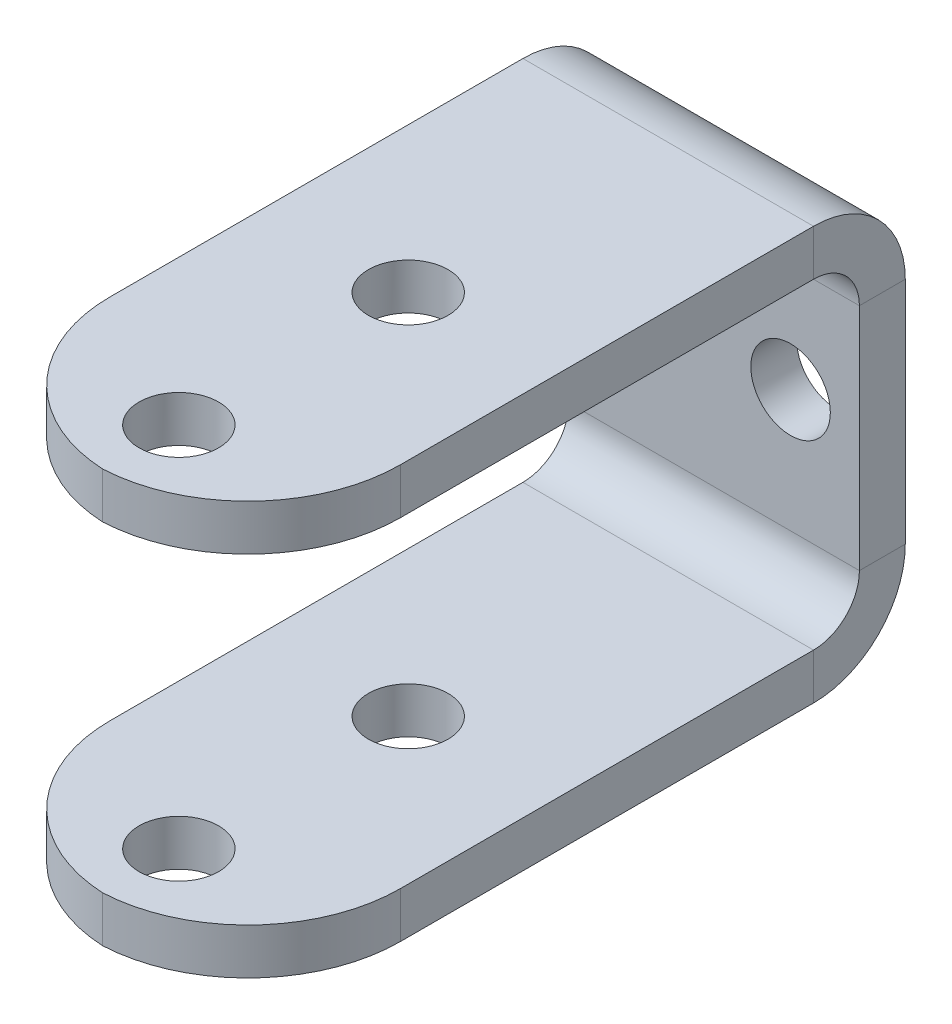
SolidWorks part; units mm, degrees
note: The reader was unsure of these and kept them because the rebuilt part matched: flange length of "Edge-Flange1".
ref_plane "Front Plane" through (0, 0, 0) normal (0, 0, 1) x (1, 0, 0)
ref_plane "Top Plane" through (0, 0, 0) normal (0, 1, 0) x (1, 0, 0)
ref_plane "Right Plane" through (0, 0, 0) normal (1, 0, 0) x (0, 0, -1)
sketch "Sketch1" plane through (0, 0, 0) normal (0, 0, 1) x (1, 0, 0)
  line L1 (-9.5, -13.5) -> (9.5, -13.5)
  line L2 (-9.5, -13.5) -> (-9.5, 13.5)
  line L3 (-9.5, 13.5) -> (9.5, 13.5)
  line L4 (9.5, -13.5) -> (9.5, 13.5)
  line L5 (-9.5, -13.5) -> (9.5, 13.5) construction
  line L6 (-9.5, 13.5) -> (9.5, -13.5) construction
  point P0 (0, 0)
  dimension "D1" = 19
  dimension "D2" = 27
base flange "Base-Flange1" sketch "Sketch1" thickness 3 reverse thickness direction no parameters "D1"=3
edge flange "Edge-Flange1" sketch "Sketch10" flange profiles "Sketch10", "Sketch11" flange angle 90 flange length 40 flange position material inside bend radius 3 thickness 3 relief rectangular parameters "D6"=10, "D8"=1
sketch "Sketch10" plane through (0, 13.5, 0) normal (0, 1, 0) x (-1, 0, 0)
  line L0 (-9.5, 0) -> (9.5, 0) construction
  line L1 (-9.5, 0) -> (9.5, 0)
  line L2 (-9.5, 0) -> (-9.5, 40)
  line L3 (-9.5, 40) -> (9.5, 40)
  line L4 (9.5, 40) -> (9.5, 0)
sketch "Sketch11" plane through (0, -13.5, 0) normal (0, -1, 0) x (1, 0, 0)
  line L0 (-9.5, 0) -> (9.5, 0) construction
  line L1 (-9.5, 0) -> (9.5, 0)
  line L2 (-9.5, 0) -> (-9.5, 40)
  line L3 (-9.5, 40) -> (9.5, 40)
  line L4 (9.5, 40) -> (9.5, 0)
bend "EdgeBend1" bend radius 3 bend angle 90 parameters "D5"=1
bend "EdgeBend2" bend radius 3 bend angle 90 parameters "D5"=2
sketch "Sketch12" plane through (0, 0, 0) normal (0, 0, 1) x (1, 0, 0)
  line L0 (0, 6.9893) -> (0, -6.026) construction
  line L1 (-9.5, 7.5) -> (9.5, 7.5) construction
  circle A0 centre (5, 0.5) radius 2.6
  circle A1 centre (-5, 0.5) radius 2.6
  dimension "D2" = 5.2
  dimension "D1" = 5
  dimension "D3" = 7
extrude "Cut-Extrude1" cut sketch "Sketch12" against normal blind 10 normal cut yes
sketch "Sketch13" plane through (0, 13.5, 0) normal (0, 1, 0) x (1, 0, 0)
  line L0 (0, -5.2652) -> (0, -28.0792) construction
  line L1 (-9.5, -40) -> (9.5, -40) construction
  circle A0 centre (0, -35) radius 2.6
  circle A1 centre (0, -20) radius 2.6
  point P5 (0, 0)
  dimension "D1" = 5.2
  dimension "D2" = 15
  dimension "D3" = 5
extrude "Cut-Extrude2" cut sketch "Sketch13" against normal through all normal cut yes
fillet "Fillet1" radius 10 4 edges at (-9.5, -12, 40) (-9.5, 12, 40) (9.5, -12, 40) (9.5, 12, 40)
sketch "Bend-Lines1" [suppressed] plane through (0, 0, 0) normal (0, 1, 0) x (1, 0, 0)
sketch "Bounding-Box1" [suppressed] plane through (0, 0, 0) normal (0, 1, 0) x (1, 0, 0)
sheet metal parameters "Sheet-Metal1" thickness 3 parameters "D1"=3
flat pattern "Flat-Pattern1" [suppressed]
sketch "Bend-Lines2" plane through (0, 0, 0) normal (0, 1, 0) x (1, 0, 0)
sketch3d "Bounding-Box2" [suppressed]
  line L0 (-12.5, 12.5, 0) -> (-12.5, -12.5, 0) construction
  line L1 (12.5, 12.5, 0) -> (12.5, -12.5, 0) construction
  line L2 (-12.5, 12.5, 0) -> (12.5, 12.5, 0) construction
  line L3 (-12.5, -12.5, 0) -> (12.5, -12.5, 0) construction
sheet metal parameters "Sheet-Metal2" thickness 3 parameters "D1"=3
flat pattern "Flat-Pattern1"
sketch "Bend-Lines2" plane through (0, 0, 0) normal (0, 0, 1) x (1, 0, 0)
  line L0 (-12.5, -10.0343) -> (12.5, -10.0343) construction
  line L1 (12.5, 10.0343) -> (-12.5, 10.0343) construction
  line L2 (-12.5, -10.0343) -> (12.5, -10.0343) construction
  line L3 (12.5, 10.0343) -> (-12.5, 10.0343) construction
sketch3d "Bounding-Box2" [suppressed]
  line L0 (12.5, 40.5686, 0) -> (12.5, -40.5686, 0) construction
  line L1 (-12.5, 40.5686, 0) -> (-12.5, -40.5686, 0) construction
  line L2 (12.5, 40.5686, 0) -> (-12.5, 40.5686, 0) construction
  line L3 (12.5, -40.5686, 0) -> (-12.5, -40.5686, 0) construction
bend of the flat pattern "Flatten-<EdgeBend1>1"
bend of the flat pattern "Flatten-<EdgeBend2>1"
sheet metal parameters "Sheet-Metal3" thickness 3 parameters "D1"=3
flat pattern "Flat-Pattern1"
sketch "Bend-Lines2" plane through (0, 0, 0) normal (0, 0, 1) x (1, 0, 0)
  line L0 (-12.5, -10.0343) -> (12.5, -10.0343) construction
  line L1 (12.5, 10.0343) -> (-12.5, 10.0343) construction
  line L2 (-12.5, -10.0343) -> (12.5, -10.0343) construction
  line L3 (12.5, 10.0343) -> (-12.5, 10.0343) construction
sketch3d "Bounding-Box2" [suppressed]
  line L0 (12.5, 40.5686, 0) -> (12.5, -40.5686, 0) construction
  line L1 (-12.5, 40.5686, 0) -> (-12.5, -40.5686, 0) construction
  line L2 (12.5, 40.5686, 0) -> (-12.5, 40.5686, 0) construction
  line L3 (12.5, -40.5686, 0) -> (-12.5, -40.5686, 0) construction
bend of the flat pattern "Flatten-<EdgeBend1>1"
bend of the flat pattern "Flatten-<EdgeBend2>1"
sheet metal parameters "Sheet-Metal4" thickness 3 parameters "D1"=3
flat pattern "Flat-Pattern1"
sketch "Bend-Lines2" plane through (0, 0, 0) normal (0, 0, 1) x (1, 0, 0)
  line L0 (-9.5, -11.0343) -> (9.5, -11.0343) construction
  line L1 (9.5, 11.0343) -> (-9.5, 11.0343) construction
  line L2 (-9.5, -11.0343) -> (9.5, -11.0343) construction
  line L3 (9.5, 11.0343) -> (-9.5, 11.0343) construction
sketch3d "Bounding-Box2" [suppressed]
  line L0 (9.5, 51.5561, 0) -> (9.5, -51.5561, 0) construction
  line L1 (-9.5, 51.5561, 0) -> (-9.5, -51.5561, 0) construction
  line L2 (9.5, 51.5561, 0) -> (-9.5, 51.5561, 0) construction
  line L3 (9.5, -51.5561, 0) -> (-9.5, -51.5561, 0) construction
bend of the flat pattern "Flatten-<EdgeBend1>1"
bend of the flat pattern "Flatten-<EdgeBend2>1"
